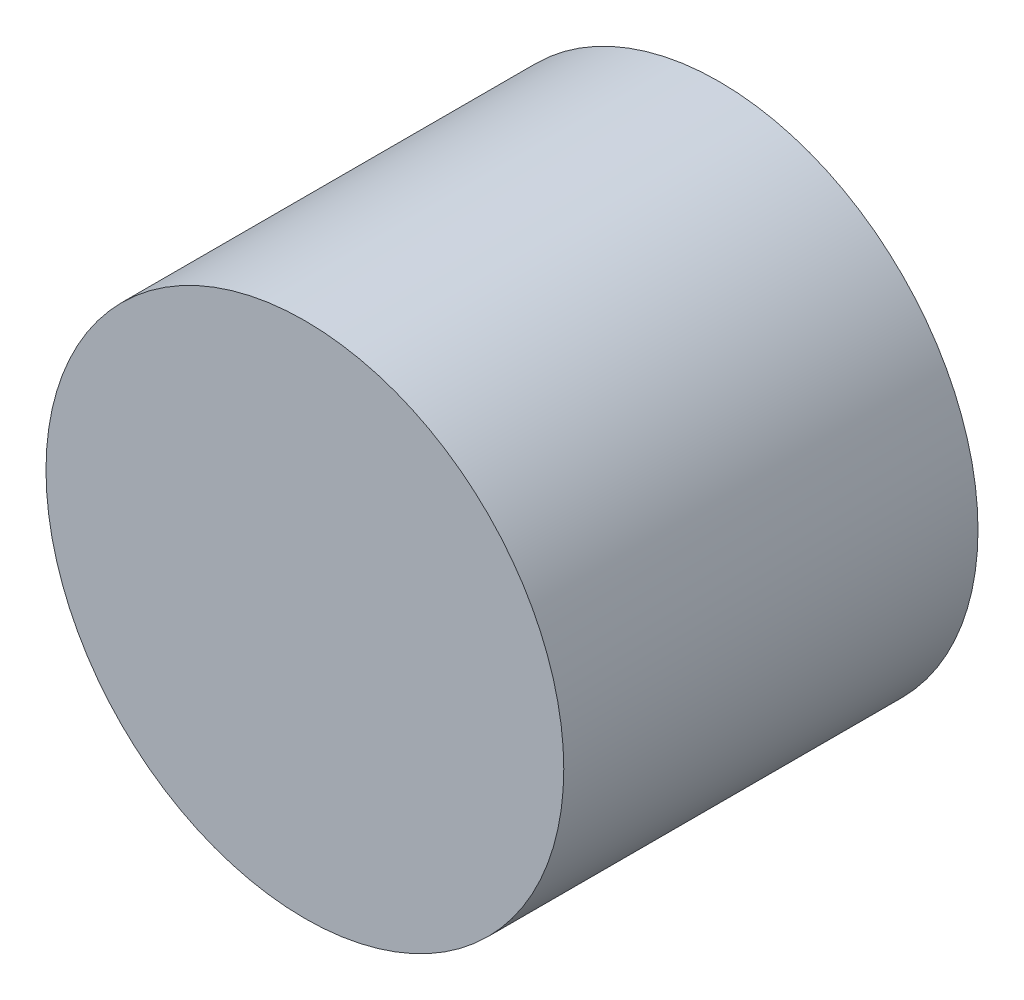
SolidWorks part; units mm, degrees
ref_plane "Front Plane" through (0, 0, 0) normal (0, 0, 1) x (1, 0, 0)
ref_plane "Top Plane" through (0, 0, 0) normal (0, 1, 0) x (1, 0, 0)
ref_plane "Right Plane" through (0, 0, 0) normal (1, 0, 0) x (0, 0, -1)
sketch "Sketch1" plane through (0, 0, 0) normal (0, 0, 1) x (1, 0, 0)
  circle A0 centre (0, 0) radius 5.25
  circle A1 centre (0, 0) radius 6.25
  dimension "D1" = 10.5
  dimension "D2" = 12.5
extrude "Boss-Extrude1" add sketch "Sketch1" along normal blind 10 contours A1
extrude "Cut-Extrude1" cut sketch "Sketch1<3>" along normal blind 8 contours A0
sketch "Sketch1<3>" plane through (0, 0, 0) normal (0, 0, 1) x (1, 0, 0) same geometry as "Sketch1"
